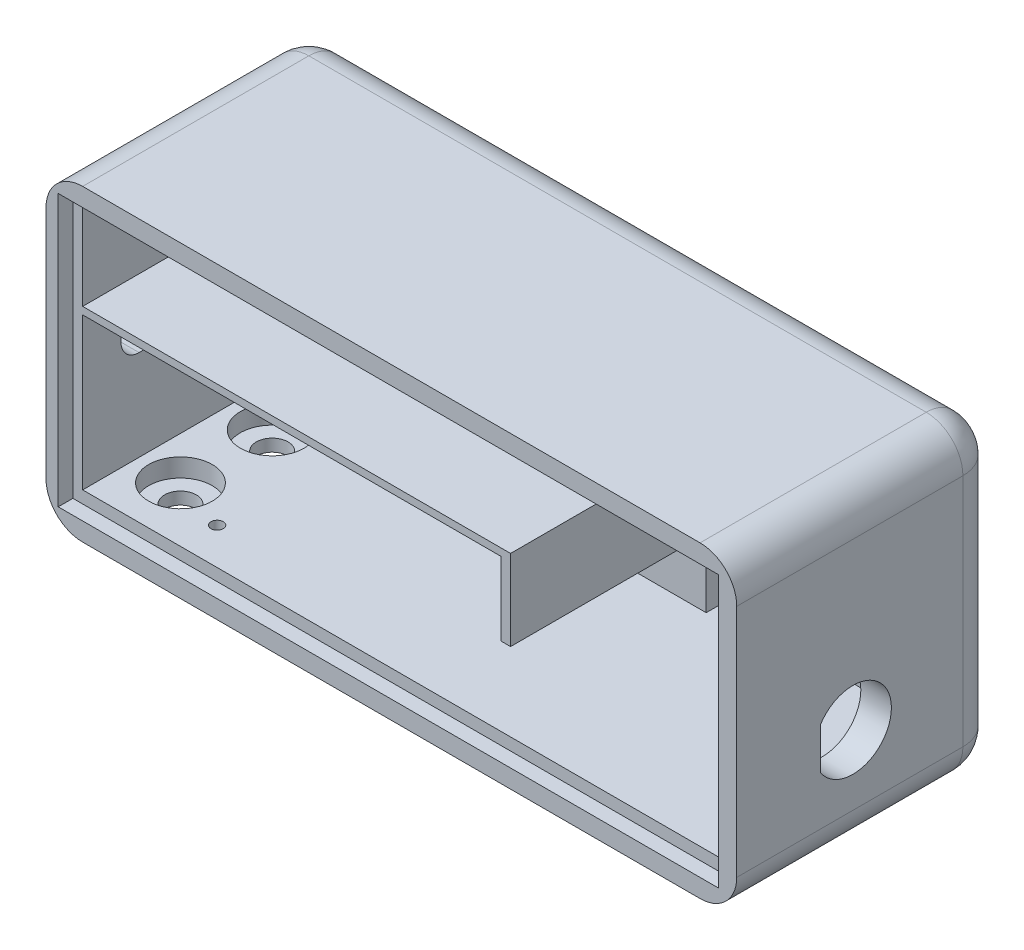
SolidWorks part; units mm, degrees
ref_plane "Спереди" through (0, 0, 0) normal (0, 0, 1) x (1, 0, 0)
ref_plane "Сверху" through (0, 0, 0) normal (0, 1, 0) x (1, 0, 0)
ref_plane "Справа" through (0, 0, 0) normal (1, 0, 0) x (0, 0, -1)
sketch "Эскиз1" plane through (0, 0, 0) normal (0, 0, 1) x (1, 0, 0)
  line L1 (-48.7675, -989.1898) -> (3.4325, -989.1898)
  line L2 (-48.7675, -989.1898) -> (-48.7675, -996.3898)
  line L3 (-48.7675, -1009.3898) -> (3.4325, -1009.3898)
  line L4 (3.4325, -989.1898) -> (3.4325, -1009.3898)
  line L6 (-48.7675, -996.9898) -> (-48.7675, -1009.3898)
  line L9 (-14.5675, -1002.9898) -> (-13.7675, -1002.9898)
  line L14 (-13.7675, -996.3898) -> (-13.7675, -996.9898)
  line L16 (-48.7675, -996.3898) -> (-13.7675, -996.3898)
  line L18 (-48.7675, -996.9898) -> (-14.5675, -996.9898)
  line L23 (-13.7675, -996.9898) -> (-13.7675, -1002.9898)
  line L25 (-14.5675, -996.9898) -> (-14.5675, -1002.9898)
  line L27 (-50.5675, -986.6898) -> (5.9325, -986.6898)
  line L28 (-50.5675, -986.6898) -> (-50.5675, -1011.8898)
  line L29 (-50.5675, -1011.8898) -> (5.9325, -1011.8898)
  line L30 (5.9325, -986.6898) -> (5.9325, -1011.8898)
  dimension "D10" = 2.5
  dimension "D5" = 35
  dimension "D8" = 6
  dimension "D11" = 1.8
  dimension "D12" = 2.5
  dimension "D13" = 2.5
extrude "Бобышка-Вытянуть1" add sketch "Эскиз1" along normal blind 19
sketch "Эскиз2" plane through (0, 0, 0) normal (0, 0, -1) x (-1, 0, 0)
  line L1 (-5.9325, -986.6898) -> (50.5675, -986.6898)
  line L2 (-5.9325, -986.6898) -> (-5.9325, -1011.8898)
  line L3 (-5.9325, -1011.8898) -> (50.5675, -1011.8898)
  line L4 (50.5675, -986.6898) -> (50.5675, -1011.8898)
extrude "Бобышка-Вытянуть2" add sketch "Эскиз2" along normal blind 2.5
sketch "Эскиз3" plane through (0, 0, 0) normal (0, 0, 1) x (1, 0, 0)
  line L0 (-48.7675, -1009.3898) -> (3.4325, -1009.3898) construction
  line L1 (-48.7675, -996.9898) -> (-14.5675, -996.9898)
  line L2 (-48.7675, -996.9898) -> (-48.7675, -1009.3898)
  line L3 (-48.7675, -1009.3898) -> (-14.5675, -1009.3898)
  line L4 (-14.5675, -996.9898) -> (-14.5675, -1009.3898)
extrude "Бобышка-Вытянуть3" add sketch "Эскиз3" along normal blind 1
sketch "Эскиз4" plane through (-50.5675, 0, 0) normal (-1, 0, 0) x (0, 0, 1)
  line L20 (14.6666, -1000.4893) -> (14.6666, -999.8893)
  line L21 (13.1866, -998.4093) -> (6.8066, -998.4093)
  line L22 (5.3266, -999.8893) -> (5.3266, -1000.4893)
  line L23 (6.8066, -1001.9693) -> (13.1866, -1001.9693)
  arc A20 (13.1866, -1001.9693) -> (14.6666, -1000.4893) centre (13.1866, -1000.4893) ccw
  arc A21 (14.6666, -999.8893) -> (13.1866, -998.4093) centre (13.1866, -999.8893) ccw
  arc A22 (6.8066, -998.4093) -> (5.3266, -999.8893) centre (6.8066, -999.8893) ccw
  arc A23 (5.3266, -1000.4893) -> (6.8066, -1001.9693) centre (6.8066, -1000.4893) ccw
extrude "Вырез-Вытянуть1" cut sketch "Эскиз4" against normal blind 1.8
sketch "Эскиз5" plane through (0, 0, 19) normal (0, 0, 1) x (1, 0, 0)
  line L0 (-48.7675, -989.1898) -> (-48.7675, -996.3898) construction
  line L1 (-49.5675, -988.1898) -> (4.4325, -988.1898)
  line L2 (-49.5675, -988.1898) -> (-49.5675, -1010.3898)
  line L3 (-49.5675, -1010.3898) -> (4.4325, -1010.3898)
  line L4 (4.4325, -988.1898) -> (4.4325, -1010.3898)
  line L5 (3.4325, -989.1898) -> (-48.7675, -989.1898) construction
  line L6 (-14.5675, -1009.3898) -> (3.4325, -1009.3898) construction
  line L7 (3.4325, -1009.3898) -> (3.4325, -989.1898) construction
  dimension "D1" = 0.8
  dimension "D2" = 1
  dimension "D3" = 1
  dimension "D4" = 1
extrude "Вырез-Вытянуть2" cut sketch "Эскиз5" against normal blind 1.2
sketch "Эскиз7" plane through (5.9325, 0, 0) normal (1, 0, 0) x (0, 0, -1)
  line L0 (-17.8, -996.9898) -> (-1, -996.9898) construction
  line L2 (0, -1009.3898) -> (0, -989.1898) construction
  line L3 (-12.15, -1001.4868) -> (-12.15, -1004.8927)
  arc A0 (-12.15, -1004.8927) -> (-12.15, -1001.4868) centre (-9.5, -1003.1898) ccw
  dimension "D1" = 6.3
  dimension "D2" = 6.2
  dimension "D3" = 9.5
extrude "Вырез-Вытянуть3" cut sketch "Эскиз7" against normal blind 4.2
fillet "Скругление1" radius 3 4 edges at (-22.3175, -986.6898, -2.5) (-50.5675, -999.2898, -2.5) (-22.3175, -1011.8898, -2.5) (5.9325, -999.2898, -2.5)
fillet "Скругление2" radius 3 8 edges at (5.0538, -1011.0111, -1.6213) (5.0538, -987.5684, -1.6213) (5.9325, -1011.8898, 9.75) (5.9325, -986.6898, 9.75) (-49.6888, -1011.0111, -1.6213) (-49.6888, -987.5684, -1.6213) (-50.5675, -1011.8898, 9.75) (-50.5675, -986.6898, 9.75)
sketch "Эскиз8" plane through (0, -1011.8898, 0) normal (0, -1, 0) x (1, 0, 0)
  line L0 (-48.7675, 1) -> (-14.5675, 1) construction
  line L1 (-48.7675, 17.8) -> (-48.7675, 1) construction
  circle A0 centre (-45.2675, 5.8) radius 1.3
  circle A1 centre (-45.2675, 13.3) radius 1.3
  dimension "D1" = 2.6
  dimension "D2" = 4.8
  dimension "D3" = 3.5
  dimension "D4" = 2
extrude "Вырез-Вытянуть4" cut sketch "Эскиз8" against normal blind 4.2
sketch "Эскиз9" plane through (0, -1009.3898, 0) normal (0, 1, 0) x (1, 0, 0)
  circle A0 centre (-45.2675, -5.8) radius 2.6
  circle A1 centre (-45.2675, -13.3) radius 2.6
  dimension "D1" = 5.2
  dimension "D2" = 2
extrude "Вырез-Вытянуть5" cut sketch "Эскиз9" against normal blind 1.5
sketch "Эскиз10" plane through (0, -1011.8898, 0) normal (0, -1, 0) x (1, 0, 0)
  circle A0 centre (-40.7675, 4.8) radius 0.5
  circle A1 centre (-45.2675, 5.8) radius 1.3 construction
  circle A2 centre (-40.7675, 14.8) radius 0.5
  dimension "D1" = 1
  dimension "D2" = 4.5
  dimension "D3" = 1
  dimension "D4" = 2
extrude "Вырез-Вытянуть6" cut sketch "Эскиз10" against normal blind 4
